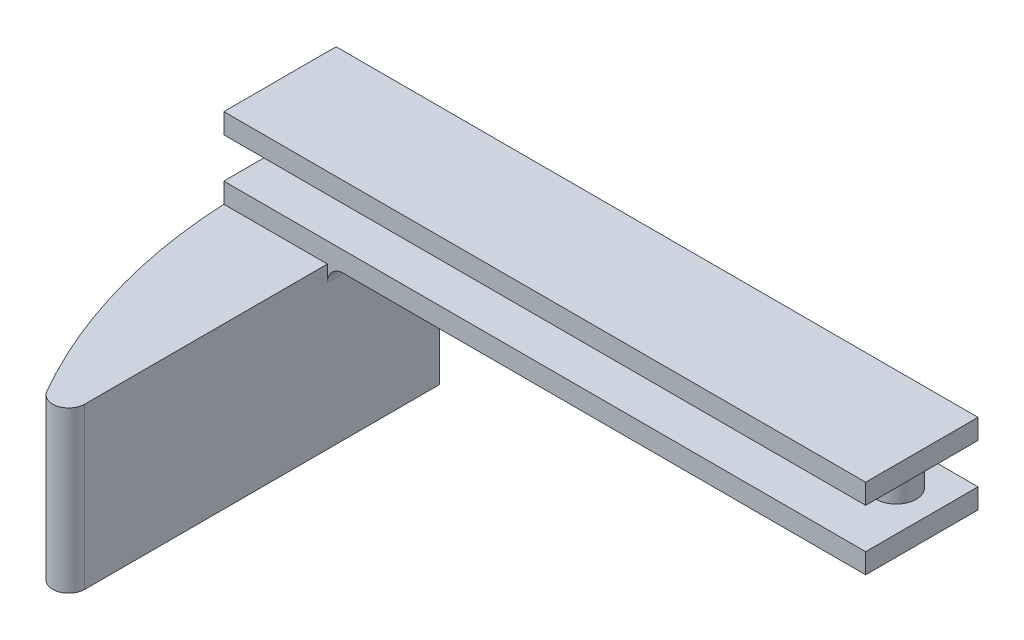
SolidWorks part; units mm, degrees
ref_plane "Front Plane" through (0, 0, 0) normal (0, 0, 1) x (1, 0, 0)
ref_plane "Top Plane" through (0, 0, 0) normal (0, 1, 0) x (1, 0, 0)
ref_plane "Right Plane" through (0, 0, 0) normal (1, 0, 0) x (0, 0, -1)
sketch "Sketch2" plane through (0, 0, 0) normal (0, 1, 0) x (1, 0, 0)
  line L1 (0, 0) -> (101.6, 0)
  line L2 (0, 0) -> (0, 17.78)
  line L3 (0, 17.78) -> (101.6, 17.78)
  line L4 (101.6, 0) -> (101.6, 17.78)
  dimension "D1" = 17.78
  dimension "D2" = 101.6
extrude "Boss-Extrude1" add sketch "Sketch2" along normal blind 3.175
sketch "Sketch3" plane through (0, 0, 0) normal (0, -1, 0) x (1, 0, 0)
  line L0 (95.25, -11.176) -> (6.35, -11.176) construction
  line L1 (95.25, -14.351) -> (6.35, -14.351)
  line L2 (95.25, -8.001) -> (6.35, -8.001)
  line L3 (0, 0) -> (101.6, 0) construction
  line L4 (0, -17.78) -> (0, 0) construction
  arc A0 (95.25, -14.351) -> (95.25, -8.001) centre (95.25, -11.176) ccw
  arc A1 (6.35, -8.001) -> (6.35, -14.351) centre (6.35, -11.176) ccw
  point P2 (50.8, -11.176)
  dimension "D1" = 88.9
  dimension "D2" = 11.176
  dimension "D3" = 6.35
  dimension "D4" = 6.35
extrude "Boss-Extrude2" add sketch "Sketch3" along normal blind 6.35 contours L2 A1 L1 A0
ref_plane "Plane1" through (0, -3.175, 0) normal (0, -1, 0) x (-1, 0, 0)
mirror "Mirror1" about plane through (0, -3.175, 0) normal (0, -1, 0) of "Boss-Extrude1"
sketch "Sketch4" plane through (0, -9.525, 0) normal (0, -1, 0) x (1, 0, 0)
  line L0 (0, 0) -> (101.6, 0) construction
  line L1 (0, -17.78) -> (16.3938, -17.78)
  line L2 (0, -17.78) -> (0, 0)
  line L4 (16.3938, -17.78) -> (16.3938, 0)
  line L5 (16.3938, 0) -> (16.3938, 47.009)
  arc A0 (0, 0) -> (16.3938, 47.009) centre (87.5, -4.1516) cw
extrude "Boss-Extrude3" add sketch "Sketch4" along normal blind 25.4
fillet "Fillet1" radius 2.54 1 edges at (16.3938, -9.525, -8.89)
fillet "Fillet2" radius 2.54 1 edges at (16.3938, -22.225, 47.009)
